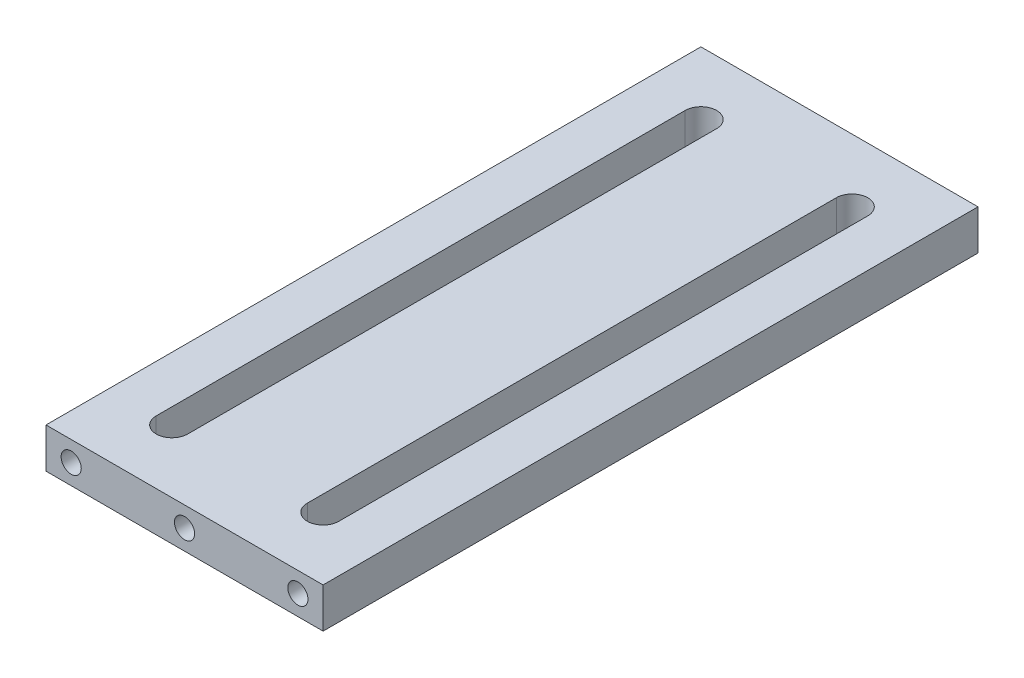
SolidWorks part; units mm, degrees
ref_plane "Front Plane" through (0, 0, 0) normal (0, 0, 1) x (1, 0, 0)
ref_plane "Top Plane" through (0, 0, 0) normal (0, 1, 0) x (1, 0, 0)
ref_plane "Right Plane" through (0, 0, 0) normal (1, 0, 0) x (0, 0, -1)
sketch "Sketch1" plane through (0, 0, 0) normal (0, 1, 0) x (1, 0, 0)
  line L1 (0, 0) -> (22, 0)
  line L2 (0, 0) -> (0, 52)
  line L3 (0, 52) -> (22, 52)
  line L4 (22, 0) -> (22, 52)
  dimension "D1" = 22
  dimension "D2" = 52
extrude "Boss-Extrude1" add sketch "Sketch1" along normal blind 3.18
sketch "Sketch2" plane through (0, 3.18, 0) normal (0, 1, 0) x (1, 0, 0)
  line L0 (5, 5) -> (5, 47) construction
  line L1 (3.75, 5) -> (3.75, 47)
  line L2 (6.25, 5) -> (6.25, 47)
  line L3 (11, 52) -> (11, 0) construction
  line L4 (22, 52) -> (0, 52) construction
  line L5 (0, 0) -> (22, 0) construction
  arc A0 (3.75, 5) -> (6.25, 5) centre (5, 5) ccw
  arc A1 (6.25, 47) -> (3.75, 47) centre (5, 47) ccw
  point P2 (5, 26)
  dimension "D2" = 2.5
  dimension "D1" = 6
  dimension "D3" = 5
  dimension "D4" = 5
extrude "Cut-Extrude1" cut sketch "Sketch2" against normal through all
ref_plane "Plane1" through (11, 0, 0) normal (1, 0, 0) x (0, 0, -1)
mirror "Mirror1" about plane through (11, 0, 0) normal (1, 0, 0) of "Cut-Extrude1"
sketch "Sketch3" plane through (0, 0, 0) normal (0, 0, 1) x (1, 0, 0)
  line L0 (0, 1.59) -> (22, 1.59) construction
  line L1 (0, 3.18) -> (0, 0) construction
  line L2 (22, 3.18) -> (22, 0) construction
  circle A0 centre (11, 1.59) radius 0.8
  circle A1 centre (2, 1.59) radius 0.8
  circle A2 centre (20, 1.59) radius 0.8
  dimension "D1" = 1.6
  dimension "D2" = 1.6
  dimension "D3" = 1.6
  dimension "D4" = 2
  dimension "D5" = 2
extrude "Cut-Extrude2" cut sketch "Sketch3" against normal blind 4
